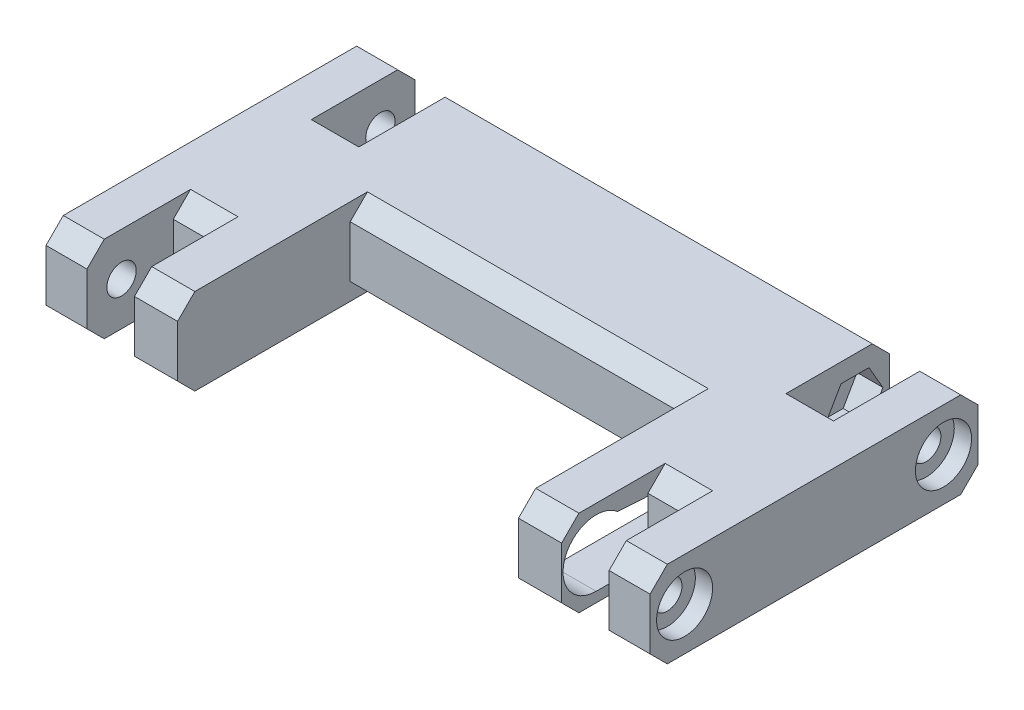
SolidWorks part; units mm, degrees
ref_plane "Front Plane" through (0, 0, 0) normal (0, 0, 1) x (1, 0, 0)
ref_plane "Top Plane" through (0, 0, 0) normal (0, 1, 0) x (1, 0, 0)
ref_plane "Right Plane" through (0, 0, 0) normal (1, 0, 0) x (0, 0, -1)
sketch "Sketch1" plane through (0, 0, 0) normal (0, 1, 0) x (1, 0, 0)
  line L1 (-35, -19) -> (35, -19)
  line L2 (-35, -19) -> (-35, 19)
  line L3 (-35, 19) -> (35, 19)
  line L4 (35, -19) -> (35, 19)
  line L5 (-35, -19) -> (35, 19) construction
  line L6 (-35, 19) -> (35, -19) construction
  point P0 (0, 0)
  dimension "D1" = 70
  dimension "D2" = 38
extrude "Boss-Extrude1" add sketch "Sketch1" along normal blind 10
sketch "Sketch2" plane through (0, 10, 0) normal (0, 1, 0) x (1, 0, 0)
  line L0 (35, 19) -> (-35, 19) construction
  line L1 (-30.25, 19) -> (-24.75, 19)
  line L2 (-30.25, 19) -> (-30.25, 9)
  line L3 (-30.25, 9) -> (-24.75, 9)
  line L4 (-24.75, 19) -> (-24.75, 9)
  line L5 (0, 0) -> (0, 19) construction
  line L6 (24.75, 19) -> (24.75, 9)
  line L7 (30.25, 9) -> (24.75, 9)
  line L8 (30.25, 19) -> (30.25, 9)
  line L9 (30.25, 19) -> (24.75, 19)
  dimension "D1" = 5.5
  dimension "D2" = 10
  dimension "D3" = 49.5
extrude "Cut-Extrude1" cut sketch "Sketch2" against normal through all
hole_wizard "CBORE for M3 Cheese Head Screw1" positions "Sketch7" profile "Sketch8" counterbore size "M3" standard "ISO" end condition up to next
sketch "Sketch7" plane through (35, 0, 0) normal (1, 0, 0) x (0, 0, -1)
  line L0 (-19, 10) -> (19, 10) construction
  line L1 (19, 10) -> (19, 0) construction
  point P0 (15, 5)
  dimension "D1" = 5
  dimension "D2" = 4
sketch "Sketch8" plane through (35, 5, -15) normal (0, 1, 0) x (0, 0, -1)
  line L0 (0, 0) -> (0, 56.75)
  line L1 (0, 56.75) -> (1.7, 56.75)
  line L3 (1.7, 56.75) -> (1.7, 2)
  line L4 (1.7, 2) -> (3.25, 2)
  line L5 (3.25, 2) -> (3.25, 0)
  line L7 (3.25, 0) -> (0, 0)
  line L11 (0, -6.35) -> (0, 107.95) construction
  dimension "Thru Hole Dia." = 3.4
  dimension "Thru Hole Depth" = 56.75
  dimension "C'Bore Dia." = 6.5
  dimension "C'Bore Depth" = 2
sketch "Sketch9" plane through (24.75, 0, 0) normal (1, 0, 0) x (0, 0, -1)
  line L1 (16.6166, 7.8) -> (13.3834, 7.8)
  line L2 (13.3834, 7.8) -> (11.7668, 5)
  line L3 (11.7668, 5) -> (13.3834, 2.2)
  line L4 (13.3834, 2.2) -> (16.6166, 2.2)
  line L5 (16.6166, 2.2) -> (18.2332, 5)
  line L6 (18.2332, 5) -> (16.6166, 7.8)
  circle A0 centre (15, 5) radius 2.8 construction
  dimension "D1" = 5.6
extrude "Cut-Extrude2" cut sketch "Sketch9" against normal blind 3
mirror "Mirror1" about plane through (0, 0, 0) normal (1, 0, 0) of "Cut-Extrude2", "CBORE for M3 Cheese Head Screw1"
mirror "Mirror2" about plane through (0, 0, 0) normal (0, 0, 1) of "Cut-Extrude1", "CBORE for M3 Cheese Head Screw1", "Cut-Extrude2", "Mirror1"
chamfer "Chamfer1" distance 2 angle 45 12 edges at (32.625, 0, -19) (32.625, 10, -19) (0, 0, -19) (0, 10, -19) (-32.625, 0, -19) (-32.625, 10, -19) (-32.625, 0, 19) (32.625, 0, 19) (0, 0, 19) (32.625, 10, 19) (-32.625, 10, 19) (0, 10, 19)
sketch "Sketch10" plane through (0, 10, 0) normal (0, 1, 0) x (1, 0, 0)
  line L0 (24.75, -19) -> (-24.75, -19) construction
  line L1 (-19.75, -19) -> (19.75, -19)
  line L2 (-19.75, -19) -> (-19.75, 1)
  line L3 (-19.75, 1) -> (19.75, 1)
  line L4 (19.75, -19) -> (19.75, 1)
  line L6 (-24.75, -9) -> (-24.75, -17) construction
  line L7 (24.75, -17) -> (24.75, -9) construction
  dimension "D1" = 5
  dimension "D2" = 20
  dimension "D3" = 5
extrude "Cut-Extrude3" cut sketch "Sketch10" against normal through all
chamfer "Chamfer2" distance 2 angle 45 2 edges at (0, 0, -1) (0, 10, -1)
chamfer "Chamfer3" distance 2 angle 45 8 edges at (27.5, 0, -9) (27.5, 10, -9) (-27.5, 0, 9) (-27.5, 0, -9) (-27.5, 10, 9) (-27.5, 10, -9) (27.5, 0, 9) (27.5, 10, 9)
sketch "Sketch11" plane through (19.75, 0, 0) normal (-1, 0, 0) x (0, 0, 1)
  line L0 (15, 1.1631) -> (-0.14, 1.1631)
  line L1 (12.5094, 7.9187) -> (-0.3177, 7.1579)
  line L2 (-3.1355, 3.9976) -> (18.831, 5.2118) construction
  line L3 (18.831, 5.2118) -> (18.7094, 7.412) construction
  line L4 (-3.1355, 3.9976) -> (-3.273, 6.4854) construction
  arc A0 (15, 1.1631) -> (12.5094, 7.9187) centre (15, 5) ccw
  arc A1 (-0.3177, 7.1579) -> (-0.14, 1.1631) centre (-0.14, 4.1631) ccw
  dimension "D1" = 22
  dimension "D2" = 3
  dimension "D3" = 7.2
extrude "Cut-Extrude4" cut sketch "Sketch11" against normal blind 5
